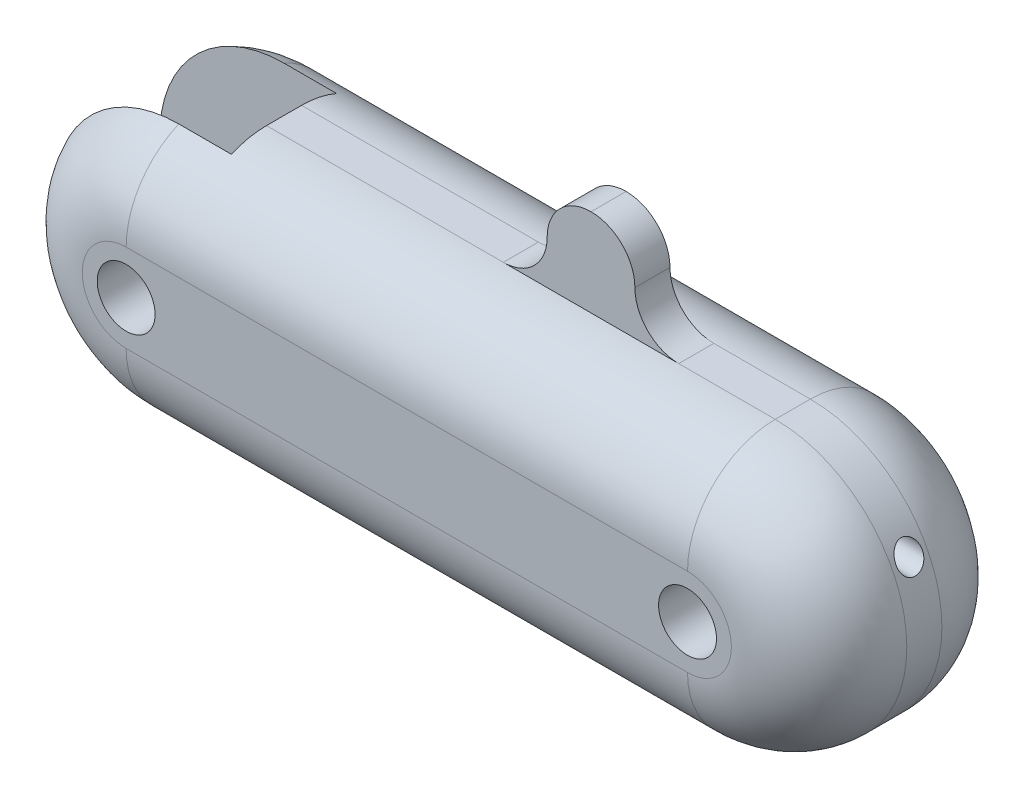
SolidWorks part; units mm, degrees
ref_plane "Front Plane" through (0, 0, 0) normal (0, 0, 1) x (1, 0, 0)
ref_plane "Top Plane" through (0, 0, 0) normal (0, 1, 0) x (1, 0, 0)
ref_plane "Right Plane" through (0, 0, 0) normal (1, 0, 0) x (0, 0, -1)
sketch "Sketch2" plane through (0, 0, 0) normal (0, 0, 1) x (1, 0, 0)
  line L0 (-16, 0) -> (16, 0)
  line L1 (-16, -15) -> (16, -15)
  arc A0 (-16, 0) -> (-16, -15) centre (-16, -7.5) ccw
  arc A1 (16, 0) -> (16, -15) centre (16, -7.5) cw
  point P4 (0, 0)
  dimension "D5" = 7.5
  dimension "D1" = 32
  dimension "D6" = 32
extrude "Boss-Extrude1" add sketch "Sketch2" along normal blind 12
fillet "Fillet1" radius 5 8 edges at (23.5, -7.5, 0) (0, -15, 0) (-23.5, -7.5, 0) (23.5, -7.5, 12) (0, -15, 12) (-23.5, -7.5, 12) (0, 0, 0) (0, 0, 12)
sketch "Sketch3" plane through (0, 0, 12) normal (0, 0, 1) x (1, 0, 0)
  circle A0 centre (-16, -7.5) radius 1.65
  circle A1 centre (16, -7.5) radius 1.65
  arc A4 (-16, -5) -> (-16, -10) centre (-16, -7.5) ccw construction
  point P4 (0, 0)
  point P6 (0, 0)
  point P7 (0, 0)
  point P11 (-18.5, -7.5)
  dimension "D1" = 3.3
ref_plane "Plane1" through (8.5, 0, 0) normal (-1, 0, 0) x (0, 0, 1)
ref_plane "Plane3" through (0, -25, 0) normal (0, -1, 0) x (-1, 0, 0)
sketch "Sketch5" plane through (0, -25, 0) normal (0, -1, 0) x (-1, 0, 0)
  line L1 (13, -3) -> (23.5, -3)
  line L2 (13, -3) -> (13, -9)
  line L3 (13, -9) -> (23.5, -9)
  line L4 (23.5, -3) -> (23.5, -9)
  line L6 (23.1235, -12) -> (13.8696, -12) construction
  line L7 (23.5, -7) -> (23.5, -5) construction
  point P4 (13, -6)
  dimension "D1" = 3
  dimension "D2" = 3
  dimension "D3" = 13
extrude "Cut-Extrude3" cut sketch "Sketch5" against normal through all
sketch "Sketch6" plane through (0, 0, 0) normal (0, 1, 0) x (1, 0, 0)
  line L0 (13.75, -12) -> (13.75, 0) construction
  line L1 (3, -5) -> (8, -5)
  line L2 (3, -5) -> (3, -7)
  line L3 (3, -7) -> (8, -7)
  line L4 (8, -5) -> (8, -7)
  line L5 (16, -7) -> (16, -12) construction
  line L6 (16, -5) -> (-13, -5) construction
  point P4 (8, -6)
  point P7 (13.75, -6)
  dimension "D1" = 5
  dimension "D3" = 8
extrude "Boss-Extrude2" add sketch "Sketch6" along normal blind 5
fillet "Fillet2" radius 2.5 2 edges at (8, 5, 6) (3, 5, 6)
fillet "Fillet3" radius 2.5 2 edges at (3, 0, 6) (8, 0, 6)
extrude "Cut-Extrude4" cut sketch "Sketch3" against normal through all
ref_plane "Plane4" through (23.5, 0, 0) normal (1, 0, 0) x (0, 0, -1)
sketch "Sketch8" plane through (23.5, 0, 0) normal (1, 0, 0) x (0, 0, -1)
  line L0 (-7, -15) -> (-5, -15) construction
  circle A0 centre (-6, -4) radius 0.75
  point P6 (-6, -15)
  dimension "D1" = 1.5
  dimension "D2" = 4
extrude "Cut-Extrude7" cut sketch "Sketch8" against normal through all
sketch "Sketch9" plane through (-13, 0, 0) normal (-1, 0, 0) x (0, 0, 1)
  line L1 (7, -15) -> (5, -15) construction
  circle A0 centre (6, -11) radius 0.75
  dimension "D1" = 1.5
  dimension "D2" = 4
sketch "Sketch10" plane through (0, -15, 0) normal (0, -1, 0) x (1, 0, 0)
  line L0 (16, 7) -> (16, 5) construction
  line L2 (16, 12) -> (16, 7) construction
  circle A0 centre (10, 6) radius 0.75
  point P5 (16, 6)
  point P10 (16, 9.5)
  dimension "D1" = 1.5
  dimension "D2" = 6
sketch "Sketch11" plane through (0, 0, 12) normal (0, 0, 1) x (1, 0, 0)
  line L0 (-13, -11) -> (10, -15) construction
  line L1 (-13, -10.25) -> (-13, -11.75) construction
  line L2 (9.25, -15) -> (10.75, -15) construction
extrude "Cut-Extrude9" cut sketch "Sketch9" along direction (0.9852, -0.1713, 0) on the side against the normal up to vertex (23 mm away) contours A0 up to point (10, -15, 6)
